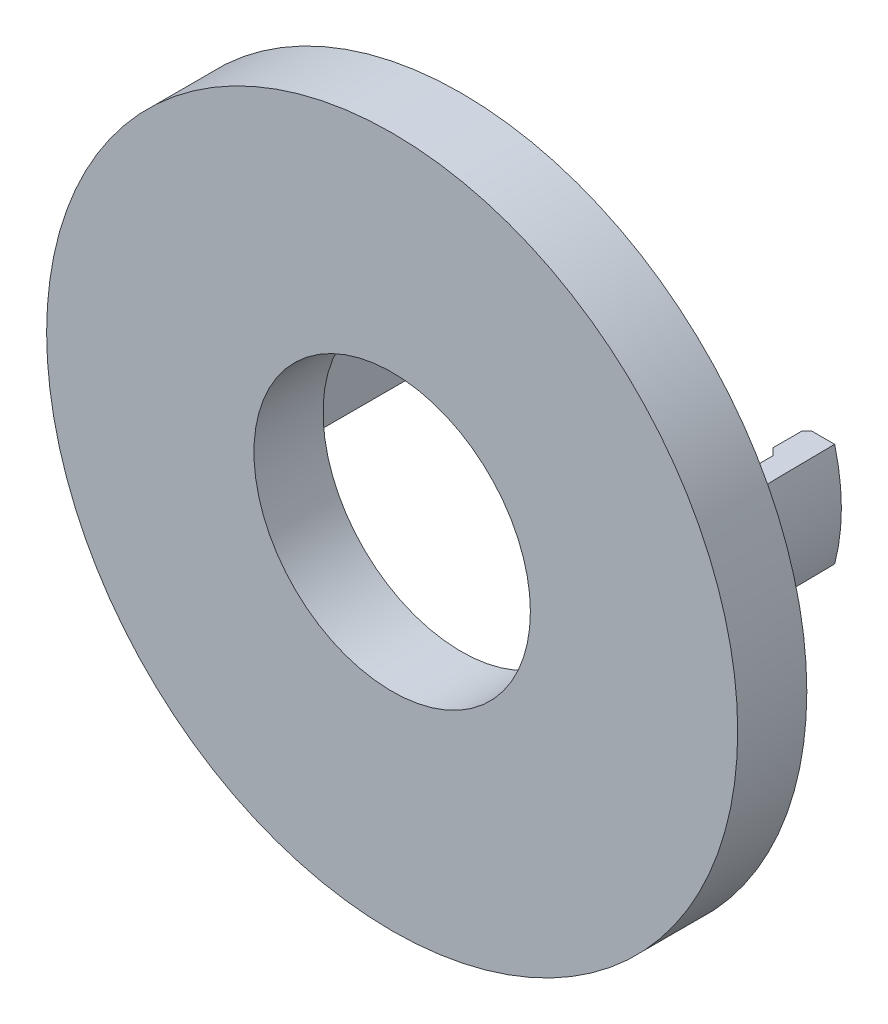
SolidWorks part; units mm, degrees
ref_plane "Front" through (0, 0, 0) normal (0, 0, 1) x (1, 0, 0)
ref_plane "Top" through (0, 0, 0) normal (0, 1, 0) x (1, 0, 0)
ref_plane "Right" through (0, 0, 0) normal (1, 0, 0) x (0, 0, -1)
sketch "Guard base" plane through (0, 0, 0) normal (0, 0, 1) x (1, 0, 0)
  circle A0 centre (0, 0) radius 25
  dimension "D1" = 50
extrude "Guard" add sketch "Guard base" along normal blind 5
sketch "Inner axle hole base" plane through (0, 0, 5) normal (0, 0, 1) x (1, 0, 0)
  circle A0 centre (0, 0) radius 10
  dimension "D1" = 20
extrude "Inner axle hole" cut sketch "Inner axle hole base" against normal through all
sketch "Coupling tooth base" plane through (0, 0, 0) normal (0, 1, 0) x (1, 0, 0)
  line L0 (10, 0) -> (15.5, 0) construction
  line L1 (15.5, 0) -> (15.5, 13)
  line L2 (12.5, 2.5) -> (12.5, 9) construction
  line L3 (15.5, 13) -> (12.5, 13) construction
  line L4 (12.5, 13) -> (11.5, 12) construction
  line L5 (11.5, 10) -> (12.5, 9) construction
  line L6 (14.75, 7.0619) -> (14.75, 18.4381) construction
  line L7 (12.75, 9.8107) -> (12.75, 2.3964)
  line L8 (12.5, 2.5) -> (10, 0) construction
  line L9 (12.75, 9.8107) -> (12.25, 10.3107)
  line L10 (11.5, 12) -> (11.5, 10) construction
  line L11 (12.25, 10.3107) -> (12.25, 12.3964)
  line L12 (15.5, 0) -> (15.5, 12.75) construction
  line L13 (15.5, 0) -> (10.3536, 0)
  line L14 (12.75, 2.3964) -> (10.3536, 0)
  line L15 (12.25, 12.3964) -> (12.6036, 12.75)
  line L16 (12.6036, 12.75) -> (15.5, 12.75)
  line L17 (15.5, 12.75) -> (25, 12.75)
  line L18 (25, 12.75) -> (25, 0)
  line L19 (25, 0) -> (15.5, 0)
  spline S0 degree 2 poles (14.75, 12.75) (14.75, 3.4464) (15.5, 0) knots 0 0 0 1 1 1
  dimension "D2" = 1
  dimension "D3" = 4
  dimension "D4" = 13
  dimension "D5" = 4
  dimension "D6" = 0.25
  dimension "D7" = 0.25
  dimension "D8" = 0.25
  dimension "D9" = 0.75
  dimension "D10" = 225
  dimension "D11" = 5.5
  dimension "D12" = 0.25
  dimension "D13" = 135
  dimension "D14" = 0.75
  dimension "D15" = 0.75
extrude "Coupling tooth" add sketch "Coupling tooth base" along normal blind 3.75 and the other way blind 3.75 contours L16 L15 L11 L9 L7 L14 | L12 L16 region at (15.1845, 0, -7.6129) region at (13.6318, 0, -5.8006)
ref_axis "Center Z" through (0, 0, 0) along (0, 0, -1)
revolve "Circularity cut" cut sketch "Sketch6<4>" angle 360 about axis through (0, 0, 0) along (0, 0, -1) region at (15.1845, 0, -7.6129) region at (20.25, 0, -6.375)
sketch "Sketch6<4>" plane through (0, 0, 0) normal (0, 1, 0) x (1, 0, 0) same geometry as "Coupling tooth base"
mirror "Coutpling teeth" about plane through (0, 0, 0) normal (1, 0, 0) of "Coupling tooth", "Circularity cut"
equation "\"mate_room\"= 0.25"
equation "\"D6@Coupling tooth base\"=\"mate_room\""
equation "\"D8@Coupling tooth base\"=\"mate_room\""
equation "\"D7@Coupling tooth base\"=\"mate_room\""
equation "\"D9@Coupling tooth base\"=\"removal_room\""
equation "\"D12@Coupling tooth base\"=\"mate_room\""
equation "\"D14@Coupling tooth base\"=\"removal_room\""
equation "\"removal_room\"= 0.75"
equation "\"large_inner_axle_diameter\"=20"
equation "\"D1@Inner axle hole base\"=\"large_inner_axle_diameter\""
equation "\"guard_thickness\"=5"
equation "\"spool_inner_diameter_room\"=1"
equation "\"32_92_coupling_tooth_height\"=13"
equation "\"32_92_coupling_tooth_thickness_total\"=4"
equation "\"32_92_coupling_tooth_protrusion\"=1"
equation "\"32_92_coupling_tooth_depth\"=8"
equation "\"32_92_coupling_tooth_base_thickness\"=5.5"
equation "\"D1@Guard\"=\"guard_thickness\""
equation "\"32_92_guard_diameter\"=50"
equation "\"D1@Guard base\"=\"32_92_guard_diameter\""
equation "\"D4@Coupling tooth base\"=\"32_92_coupling_tooth_height\""
equation "\"D3@Coupling tooth base\"=\"32_92_coupling_tooth_thickness_total\""
equation "\"D2@Coupling tooth base\"=\"32_92_coupling_tooth_protrusion\""
equation "\"D11@Coupling tooth base\"=\"32_92_coupling_tooth_base_thickness\""
equation "\"32_92_coupling_tooth_head_height\"=4"
equation "\"D5@Coupling tooth base\"=\"32_92_coupling_tooth_head_height\""
equation "\"32_92_spool_inner_diameter\"=32"
equation "\"32_92_spool_thickness\"=92"
